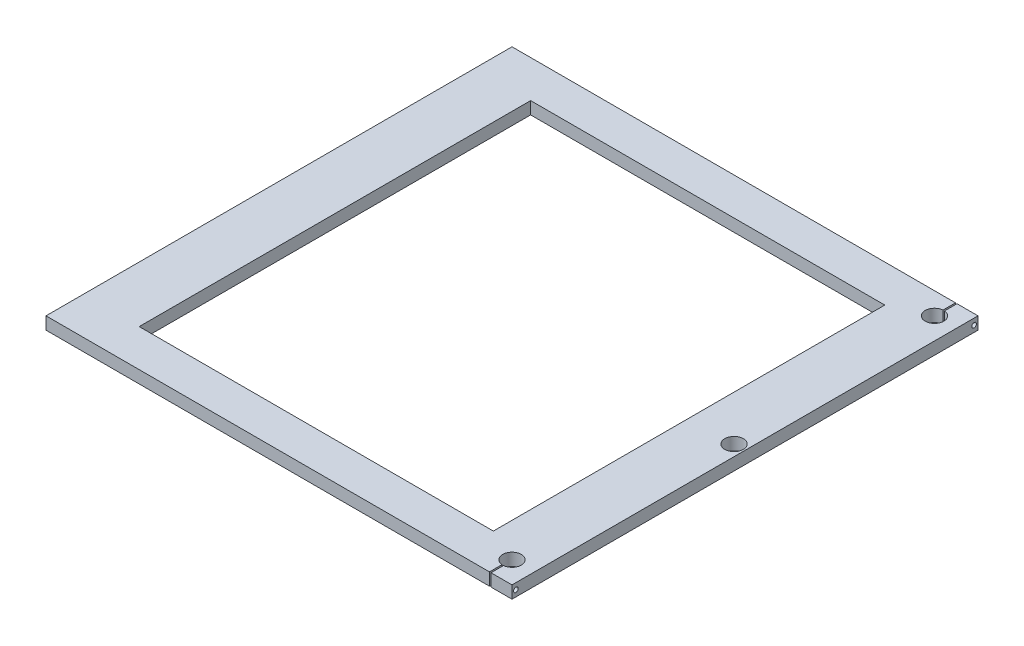
SolidWorks part; units mm, degrees
ref_plane "Front Plane" through (0, 0, 0) normal (0, 0, 1) x (1, 0, 0)
ref_plane "Top Plane" through (0, 0, 0) normal (0, 1, 0) x (1, 0, 0)
ref_plane "Right Plane" through (0, 0, 0) normal (1, 0, 0) x (0, 0, -1)
sketch "Sketch1" plane through (0, 0, 0) normal (0, 1, 0) x (1, 0, 0)
  line L0 (150, 150) -> (150, -150)
  line L1 (-150, -150) -> (150, -150)
  line L2 (-150, -150) -> (-150, 150)
  line L3 (-150, 150) -> (150, 150)
  line L5 (-150, -150) -> (150, 150) construction
  line L6 (-150, 150) -> (150, -150) construction
  line L7 (-114, -126) -> (114, -126)
  line L8 (-114, -126) -> (-114, 126)
  line L9 (-114, 126) -> (114, 126)
  line L10 (114, -126) -> (114, 126)
  line L11 (-114, -126) -> (114, 126) construction
  line L12 (-114, 126) -> (114, -126) construction
  point P0 (0, 0)
  point P5 (0, 0)
  dimension "D1" = 300
  dimension "D2" = 228
  dimension "D3" = 252
extrude "Boss-Extrude1" add sketch "Sketch1" along normal blind 8
sketch "Sketch2" plane through (0, 0, 0) normal (0, 1, 0) x (1, 0, 0)
  line L0 (150, 150) -> (-150, 150) construction
  line L1 (150, 150) -> (-150, 150) construction
  line L2 (150, -150) -> (150, 150) construction
  line L3 (135.5, 150) -> (136.5, 150)
  line L4 (135.5, 150) -> (135.5, 141.9791)
  line L6 (136.5, 150) -> (136.5, 141.9791)
  arc A0 (135.5, 141.9791) -> (136.5, 141.9791) centre (136, 136) ccw
  point P6 (136, 142)
  dimension "D1" = 12
  dimension "D2" = 14
  dimension "D3" = 14
  dimension "D4" = 1
extrude "Cut-Extrude1" cut sketch "Sketch2" along normal through all
sketch "Sketch3" plane through (150, 0, 0) normal (1, 0, 0) x (0, 0, -1)
  line L0 (147.5, 4) -> (150, 4) construction
  line L2 (150, 8) -> (150, 0) construction
  circle A0 centre (147.5, 4) radius 1.5
  dimension "D1" = 3
  dimension "D2" = 2.5
extrude "Cut-Extrude2" cut sketch "Sketch3" against normal up to surface (14.5 mm away) up to face at (135.5, 4, -145.9896)
sketch "Sketch4" plane through (0, 8, 0) normal (0, 1, 0) x (1, 0, 0)
  line L0 (136, -864) -> (136, 49136) construction
  circle A0 centre (142.9602, 0) radius 6
  dimension "D1" = 6.9602
  dimension "D2" = 12
mirror "Mirror3" about plane through (0, 0, 0) normal (0, 0, 1) of "Cut-Extrude2", "Cut-Extrude1"
extrude "Cut-Extrude4" cut sketch "Sketch4" against normal through all
